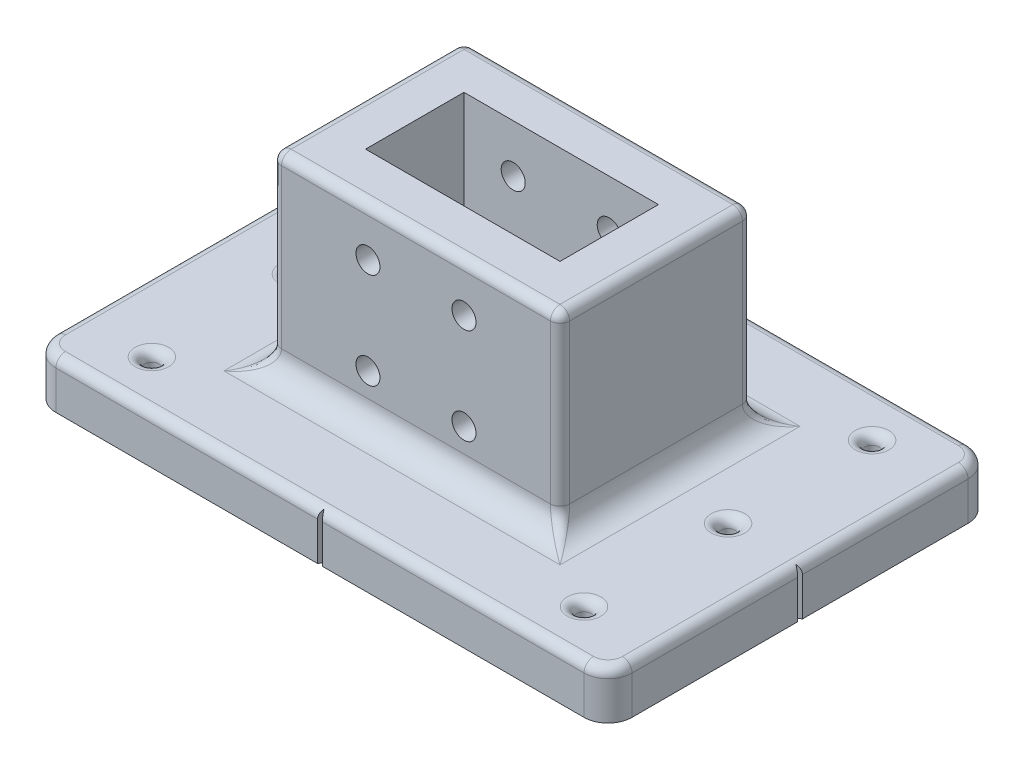
SolidWorks part; units mm, degrees
ref_plane "Piano frontale" through (0, 0, 0) normal (0, 0, 1) x (1, 0, 0)
ref_plane "Piano superiore" through (0, 0, 0) normal (0, 1, 0) x (1, 0, 0)
ref_plane "Piano destro" through (0, 0, 0) normal (1, 0, 0) x (0, 0, -1)
sketch "Schizzo1" plane through (0, 0, 0) normal (0, 1, 0) x (1, 0, 0)
  line L1 (-30, 20) -> (30, 20)
  line L2 (-30, 20) -> (-30, -20)
  line L3 (-30, -20) -> (30, -20)
  line L4 (30, 20) -> (30, -20)
  line L5 (-30, 20) -> (30, -20) construction
  line L6 (-30, -20) -> (30, 20) construction
  line L7 (-20.25, 10.25) -> (20.25, 10.25)
  line L8 (-20.25, 10.25) -> (-20.25, -10.25)
  line L9 (-20.25, -10.25) -> (20.25, -10.25)
  line L10 (20.25, 10.25) -> (20.25, -10.25)
  line L11 (-20.25, 10.25) -> (20.25, -10.25) construction
  line L12 (-20.25, -10.25) -> (20.25, 10.25) construction
  point P0 (0, 0)
  point P6 (0, 0)
  dimension "D1" = 60
  dimension "80" = 40
  dimension "D2" = 20.5
  dimension "D3" = 40.5
extrude "Estrusione-Estrusione1" add sketch "Schizzo1" along normal blind 50
sketch "Schizzo2" plane through (0, 0, 0) normal (0, -1, 0) x (1, 0, 0)
  line L0 (0, -40) -> (0, 40) construction
  line L1 (-30, 20) -> (30, 20)
  line L2 (-30, 20) -> (-30, -20)
  line L3 (-30, -20) -> (30, -20)
  line L4 (30, 20) -> (30, -20)
  line L5 (-30, 20) -> (30, -20) construction
  line L6 (-30, -20) -> (30, 20) construction
  line L7 (-60, 40) -> (60, 40)
  line L8 (-60, 40) -> (-60, -40)
  line L9 (-60, -40) -> (60, -40)
  line L10 (60, 40) -> (60, -40)
  line L11 (-60, 40) -> (60, -40) construction
  line L12 (-60, -40) -> (60, 40) construction
  line L13 (-45, -40) -> (-45, 40) construction
  circle A0 centre (-45, -30) radius 1.5
  circle A1 centre (-45, 0) radius 1.5
  circle A2 centre (-45, 30) radius 1.5
  circle A3 centre (45, 30) radius 1.5
  circle A4 centre (45, 0) radius 1.5
  circle A5 centre (45, -30) radius 1.5
  point P0 (0, 0)
  point P7 (0, 0)
  dimension "D4" = 3
  dimension "D1" = 80
  dimension "D2" = 120
  dimension "D3" = 15
extrude "Estrusione-Estrusione2" add sketch "Schizzo2" against normal blind 10
fillet "Raccordo1" radius 5 8 edges at (-60, 5, -40) (60, 5, -40) (60, 5, 40) (-60, 5, 40) (-30, 10, 0) (0, 10, -20) (30, 10, 0) (0, 10, 20)
fillet "Raccordo2" radius 2 26 edges at (58.5355, 10, -38.5355) (60, 10, 0) (58.5355, 10, 38.5355) (0, 10, 40) (-58.5355, 10, 38.5355) (-60, 10, 0) (-58.5355, 10, -38.5355) (0, 10, -40) (-45, 10, -31.5) (-45, 10, -1.5) (-45, 10, 28.5) (45, 10, 31.5) (45, 10, 1.5) (45, 10, -28.5) (-31.4645, 11.4645, -21.4645) (31.4645, 11.4645, -21.4645) (31.4645, 11.4645, 21.4645) (-31.4645, 11.4645, 21.4645) (-30, 50, 0) (0, 50, -20) (-30, 32.5, -20) (30, 50, 0) (30, 32.5, -20) (0, 50, 20) (30, 32.5, 20) (-30, 32.5, 20)
sketch "Schizzo3" plane through (0, 0, 0) normal (0, -1, 0) x (1, 0, 0)
  line L0 (0, 0) -> (0, 50000) construction
  line L1 (0, 0) -> (50000, 0) construction
  line L2 (-0.5, 40) -> (0.5, 40)
  line L3 (55, 40) -> (-55, 40) construction
  line L4 (0.5, 40) -> (0, 39.134)
  line L5 (0, 39.134) -> (-0.5, 40)
  line L6 (0.5, -40) -> (0, -39.134)
  line L7 (0, -39.134) -> (-0.5, -40)
  line L8 (-0.5, -40) -> (0.5, -40)
  line L10 (59.134, 0) -> (60, 0.5)
  line L13 (-60, 0.5) -> (-60, -0.5)
  line L14 (-60, 35) -> (-60, -35) construction
  line L15 (-60, -0.5) -> (-59.134, 0)
  line L16 (-59.134, 0) -> (-60, 0.5)
  line L17 (60, -0.5) -> (59.134, 0)
  line L18 (60, 0.5) -> (60, -0.5)
  dimension "D1" = 1
  dimension "D2" = 1
extrude "Taglio-Estrusione1" cut sketch "Schizzo3" against normal through all
sketch "Schizzo4" plane through (0, 0, 20) normal (0, 0, 1) x (1, 0, 0)
  line L0 (0, 48) -> (0, -49952) construction
  line L1 (28, 48) -> (-28, 48) construction
  line L2 (-10, 48) -> (-10, -49952) construction
  line L3 (10, 46.8377) -> (10, -49953.1623) construction
  line L4 (0, 40) -> (50000, 40) construction
  line L5 (0, 20) -> (50000, 20) construction
  line L6 (-28, 50) -> (28, 50) construction
  circle A0 centre (-10, 40) radius 2.5
  circle A1 centre (-10, 20) radius 2.5
  circle A2 centre (10, 40) radius 2.5
  circle A3 centre (10, 20) radius 2.5
  point P4 (0, 48)
  dimension "D3" = 5
  dimension "D1" = 20
  dimension "D2" = 10
  dimension "D4" = 20
  dimension "D5" = 10
extrude "Taglio-Estrusione2" cut sketch "Schizzo4" against normal through all
